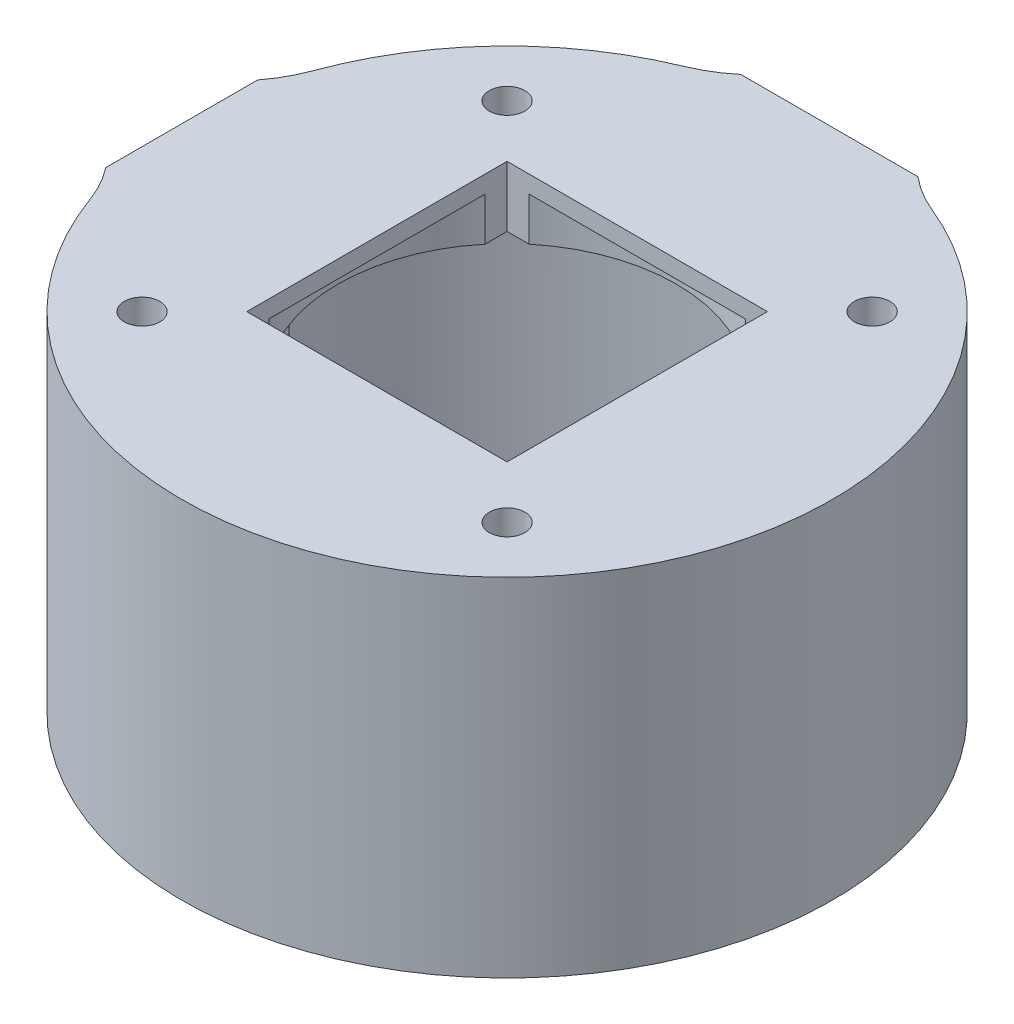
SolidWorks part; units mm, degrees
ref_plane "Спереди" through (0, 0, 0) normal (0, 0, 1) x (1, 0, 0)
ref_plane "Сверху" through (0, 0, 0) normal (0, 1, 0) x (1, 0, 0)
ref_plane "Справа" through (0, 0, 0) normal (1, 0, 0) x (0, 0, -1)
sketch "Sketch1" plane through (0, 0, 0) normal (0, 1, 0) x (1, 0, 0)
  circle A0 centre (0, 0) radius 70
  circle A1 centre (0, 0) radius 75
  dimension "D1" = 140
  dimension "D2" = 150
extrude "Boss-Extrude1" add sketch "Sketch1" along normal blind 60
sketch "Sketch2" plane through (0, 60, 0) normal (0, 1, 0) x (1, 0, 0)
  circle A0 centre (0, 0) radius 75
  circle A1 centre (0, 0) radius 75 construction
extrude "Boss-Extrude2" add sketch "Sketch2" along normal blind 20
sketch "Sketch3" plane through (0, 80, 0) normal (0, 1, 0) x (1, 0, 0)
  line L1 (42.0729, 42.0729) -> (-42.0729, 42.0729) construction
  line L2 (42.0729, 42.0729) -> (42.0729, -42.0729) construction
  line L3 (42.0729, -42.0729) -> (-42.0729, -42.0729) construction
  line L4 (-42.0729, 42.0729) -> (-42.0729, -42.0729) construction
  line L5 (42.0729, 42.0729) -> (-42.0729, -42.0729) construction
  line L6 (42.0729, -42.0729) -> (-42.0729, 42.0729) construction
  line L7 (22.5, 22.5) -> (-22.5, 22.5)
  line L8 (22.5, 22.5) -> (22.5, -22.5)
  line L9 (22.5, -22.5) -> (-22.5, -22.5)
  line L10 (-22.5, 22.5) -> (-22.5, -22.5)
  line L11 (22.5, 22.5) -> (-22.5, -22.5) construction
  line L12 (22.5, -22.5) -> (-22.5, 22.5) construction
  circle A0 centre (0, 0) radius 59.5 construction
  circle A1 centre (-42.0729, -42.0729) radius 4.1
  circle A2 centre (-42.0729, 42.0729) radius 4.1
  circle A3 centre (42.0729, 42.0729) radius 4.1
  circle A4 centre (42.0729, -42.0729) radius 4.1
  dimension "D1" = 119
  dimension "D2" = 8.2
  dimension "D3" = 45
extrude "Cut-Extrude1" cut sketch "Sketch3" against normal through all
sketch "Sketch5" plane through (0, 60, 0) normal (0, -1, 0) x (1, 0, 0)
  line L0 (0, 22.5) -> (0, 70) construction
  line L1 (-22.5, 22.5) -> (22.5, 22.5) construction
  line L3 (-22.5, 42.5) -> (22.5, 42.5)
  line L4 (-22.5, 42.5) -> (-22.5, 22.5)
  line L5 (-22.5, 22.5) -> (22.5, 22.5)
  line L6 (22.5, 42.5) -> (22.5, 22.5)
  line L7 (-22.5, 42.5) -> (22.5, 22.5) construction
  line L8 (-22.5, 22.5) -> (22.5, 42.5) construction
  circle A0 centre (0, 0) radius 70 construction
  point P7 (0, 32.5)
  dimension "D1" = 20
extrude "Cut-Extrude2" cut sketch "Sketch5" against normal blind 18
sketch "Sketch6" plane through (0, 60, 0) normal (0, -1, 0) x (1, 0, 0)
  circle A0 centre (0, 0) radius 51
  dimension "D1" = 102
extrude "Cut-Extrude3" cut sketch "Sketch6" against normal blind 6
sketch "Sketch7" plane through (0, 66, 0) normal (0, -1, 0) x (1, 0, 0)
  circle A0 centre (-42.0729, -42.0729) radius 7
  circle A1 centre (-42.0729, 42.0729) radius 7
  circle A2 centre (-42.0729, 42.0729) radius 4.1
  circle A3 centre (-42.0729, -42.0729) radius 4.1
  circle A4 centre (42.0729, -42.0729) radius 4.1
  circle A5 centre (42.0729, 42.0729) radius 4.1
  circle A6 centre (42.0729, -42.0729) radius 7
  circle A7 centre (42.0729, 42.0729) radius 7
  dimension "D1" = 14
extrude "Boss-Extrude3" add sketch "Sketch7" along normal up to surface (6 mm away) up to face at (0, 60, -51)
sketch "Sketch8" plane through (0, 66, 0) normal (0, -1, 0) x (1, 0, 0)
  circle A0 centre (0, 0) radius 39
  dimension "D1" = 78
extrude "Cut-Extrude4" cut sketch "Sketch8" against normal blind 10
sketch "Sketch9" plane through (0, 0, 0) normal (0, -1, 0) x (1, 0, 0)
  line L0 (0, -75) -> (0, 75) construction
  line L1 (7.5, -74.6241) -> (-7.5, -74.6241)
  circle A0 centre (0, 0) radius 75 construction
  point P8 (0, -74.6241)
  dimension "D1" = 15
extrude "Cut-Extrude5" cut sketch "Sketch9" against normal through all and the other way through all
sketch "Sketch10" plane through (0, 0, -74.6241) normal (0, 0, -1) x (-1, 0, 0)
  line L0 (0, 0) -> (0, 80) construction
  line L1 (-7.5, 0) -> (7.5, 0) construction
  line L2 (-7.5, 80) -> (7.5, 80) construction
  line L4 (-7.5, 20.4) -> (7.5, 20.4)
  line L5 (-7.5, 20.4) -> (-7.5, 7.6)
  line L6 (-7.5, 7.6) -> (7.5, 7.6)
  line L7 (7.5, 20.4) -> (7.5, 7.6)
  line L8 (-7.5, 20.4) -> (7.5, 7.6) construction
  line L9 (-7.5, 7.6) -> (7.5, 20.4) construction
  point P6 (0, 14)
  dimension "D1" = 12.8
  dimension "D2" = 15
  dimension "D3" = 14
  dimension "D4" = 20.4
extrude "Cut-Extrude6" cut sketch "Sketch10" against normal blind 10
sketch "Sketch11" plane through (0, 0, -74.6241) normal (0, 0, -1) x (-1, 0, 0)
  line L0 (0, 20.4) -> (0, 7.6) construction
  line L1 (7.5, 20.4) -> (-7.5, 20.4) construction
  line L2 (-7.5, 7.6) -> (7.5, 7.6) construction
  line L4 (-10, 4) -> (10, 4)
  line L5 (-10, 4) -> (-10, 24)
  line L6 (-10, 24) -> (10, 24)
  line L7 (10, 4) -> (10, 24)
  line L8 (-10, 4) -> (10, 24) construction
  line L9 (-10, 24) -> (10, 4) construction
  point P6 (0, 14)
  dimension "D1" = 20
  dimension "D2" = 20
extrude "Cut-Extrude7" cut sketch "Sketch11" against normal blind 10 from offset 3 offset against normal yes
sketch "Sketch12" plane through (0, 60, 0) normal (0, -1, 0) x (1, 0, 0)
  line L0 (0, -51) -> (0, 70) construction
  circle A0 centre (0, 0) radius 51 construction
  circle A1 centre (0, 0) radius 70 construction
  circle A2 centre (0, -51) radius 7.5
  dimension "D1" = 15
extrude "Cut-Extrude8" cut sketch "Sketch12" against normal up to surface (6 mm away) up to face at (0, 66, 19.4638)
sketch "Sketch13" plane through (0, 60, 0) normal (0, -1, 0) x (1, 0, 0)
  line L0 (-47.9479, -51) -> (0, -51) construction
  circle A0 centre (0, 0) radius 70 construction
  arc A1 (7.4797, -50.4485) -> (-7.4797, -50.4485) centre (0, 0) ccw construction
  circle A2 centre (0, -51) radius 10.5
  dimension "D1" = 21
extrude "Cut-Extrude9" cut sketch "Sketch13" against normal up to surface (6 mm away) and the other way through all up to face at (0, 66, -3.75)
sketch "Sketch14" plane through (0, 0, 0) normal (0, -1, 0) x (1, 0, 0)
  line L0 (0, 0) -> (0, -110.0571) construction
  line L2 (10, -94.282) -> (-10, -94.282)
  line L3 (10, -94.282) -> (10, -69.282)
  line L4 (10, -69.282) -> (-10, -69.282) construction
  line L5 (-10, -94.282) -> (-10, -69.282)
  line L6 (10, -94.282) -> (-10, -69.282) construction
  line L7 (10, -69.282) -> (-10, -94.282) construction
  arc A0 (-10, -69.282) -> (10, -69.282) centre (0, 0) ccw construction
  circle A1 centre (0, 0) radius 70 construction
  arc A2 (10, -69.282) -> (-10, -69.282) centre (0, 0) cw
  point P6 (0, -70)
  point P7 (0, -81.782)
  dimension "D1" = 20
  dimension "D2" = 25
  dimension "D3" = 81.782
extrude "Boss-Extrude4" add sketch "Sketch14" against normal up to surface (80 mm away) up to face at (-42.0729, 80, -37.9729)
sketch "Sketch15" plane through (0, 0, 0) normal (0, -1, 0) x (1, 0, 0)
  line L0 (0, -59.1608) -> (0, -94.282) construction
  line L2 (-10, -94.282) -> (10, -94.282) construction
  line L4 (7.55, -91.5916) -> (-7.55, -91.5916)
  line L5 (7.55, -91.5916) -> (7.55, -69.5916)
  line L6 (7.55, -69.5916) -> (-7.55, -69.5916)
  line L7 (-7.55, -91.5916) -> (-7.55, -69.5916)
  line L8 (7.55, -91.5916) -> (-7.55, -69.5916) construction
  line L9 (7.55, -69.5916) -> (-7.55, -91.5916) construction
  circle A0 centre (0, 0) radius 70 construction
  point P6 (0, -80.5916)
  dimension "D1" = 15.1
  dimension "D2" = 22
extrude "Cut-Extrude10" cut sketch "Sketch15" against normal blind 20.4
fillet "Fillet1" radius 30 2 edges at (10, 40, -74.3303) (-10, 40, -74.3303)
sketch "Sketch16" plane through (0, 20.4, 0) normal (0, -1, 0) x (1, 0, 0)
  line L0 (0, -70) -> (0, -91.5916) construction
  line L1 (-7.55, -91.5916) -> (7.55, -91.5916) construction
  line L3 (7.55, -76.1916) -> (-7.55, -76.1916)
  line L4 (7.55, -76.1916) -> (7.55, -91.5916)
  line L5 (7.55, -91.5916) -> (-7.55, -91.5916)
  line L6 (-7.55, -76.1916) -> (-7.55, -91.5916)
  line L7 (7.55, -76.1916) -> (-7.55, -91.5916) construction
  line L8 (7.55, -91.5916) -> (-7.55, -76.1916) construction
  arc A0 (-7.55, -69.5916) -> (7.55, -69.5916) centre (0, 0) ccw construction
  point P7 (0, -83.8916)
  dimension "D1" = 15.4
extrude "Cut-Extrude11" cut sketch "Sketch16" against normal blind 2
sketch "Sketch17" plane through (0, 0, -91.5916) normal (0, 0, 1) x (1, 0, 0)
  line L0 (0, 22.4) -> (0, 0) construction
  line L1 (-7.55, 22.4) -> (7.55, 22.4) construction
  line L2 (-7.55, 0) -> (7.55, 0) construction
  line L4 (7.55, 9.6) -> (-7.55, 9.6)
  line L5 (7.55, 9.6) -> (7.55, 22.4)
  line L6 (7.55, 22.4) -> (-7.55, 22.4)
  line L7 (-7.55, 9.6) -> (-7.55, 22.4)
  line L8 (7.55, 9.6) -> (-7.55, 22.4) construction
  line L9 (7.55, 22.4) -> (-7.55, 9.6) construction
  point P6 (0, 16)
  dimension "D1" = 12.8
  dimension "D2" = 15.1
extrude "Cut-Extrude12" cut sketch "Sketch17" against normal through all
chamfer "Chamfer1" distance 20 angle 65 1 edges at (0, 80, -94.282) first distance on face at (0, 80, -44.4515)
sketch "Sketch19" plane through (0, 20.4, 0) normal (0, -1, 0) x (1, 0, 0)
  line L0 (7.55, -72.2416) -> (-7.55, -72.2416) construction
  line L1 (7.55, -76.1916) -> (7.55, -69.5916) construction
  line L2 (-7.55, -69.5916) -> (-7.55, -76.1916) construction
  line L4 (-7.55, -74.8916) -> (7.55, -74.8916)
  line L5 (-7.55, -74.8916) -> (-7.55, -69.5916)
  line L6 (-7.55, -69.5916) -> (7.55, -69.5916) construction
  line L7 (7.55, -74.8916) -> (7.55, -69.5916)
  line L8 (-7.55, -74.8916) -> (7.55, -69.5916) construction
  line L9 (-7.55, -69.5916) -> (7.55, -74.8916) construction
  arc A4 (-7.55, -69.5916) -> (7.55, -69.5916) centre (0, 0) ccw
  arc A5 (7.55, -69.5916) -> (-7.55, -69.5916) centre (0, 0) ccw construction
  point P6 (0, -72.2416)
  dimension "D1" = 5.3
extrude "Boss-Extrude5" add sketch "Sketch19" along normal blind 5
sketch "Sketch20" plane through (0, 0, 0) normal (0, -1, 0) x (1, 0, 0)
  line L0 (0, 0) -> (-75, 0) construction
  line L2 (-65, -15) -> (-75, -15)
  line L3 (-65, -15) -> (-65, 15)
  line L4 (-65, 15) -> (-75, 15)
  line L5 (-75, -15) -> (-75, 15)
  line L6 (-65, -15) -> (-75, 15) construction
  line L7 (-65, 15) -> (-75, -15) construction
  arc A0 (28.4741, -69.3846) -> (-28.4741, -69.3846) centre (0, 0) ccw construction
  point P7 (-70, 0)
  point P12 (0, 0)
  point P13 (0, 0)
  point P14 (0, 0)
  point P15 (0, 0)
  point P16 (0, 0)
  point P17 (-75, 0)
  dimension "D1" = 10
  dimension "D2" = 30
extrude "Cut-Extrude13" cut sketch "Sketch20" against normal blind 30 from offset 20 offset against normal yes
sketch "Sketch21" plane through (0, 50, 0) normal (0, -1, 0) x (1, 0, 0)
  line L0 (-67.7772, 17.5) -> (-67.7772, -17.5)
  line L3 (-65.8886, 0) -> (-71.3886, 0) construction
  line L4 (-75, -17.5) -> (-67.7772, -17.5)
  line L5 (-75, -17.5) -> (-75, 17.5)
  line L6 (-75, 17.5) -> (-67.7772, 17.5)
  line L8 (-75, -17.5) -> (-67.7772, 17.5) construction
  line L9 (-75, 17.5) -> (-67.7772, -17.5) construction
  arc A1 (-73.4847, 15) -> (-73.4847, -15) centre (0, 0) ccw construction
  circle A3 centre (0, 0) radius 70 construction
  point P0 (0, 0)
  point P3 (-75, 0)
  point P12 (-71.3886, 0)
  dimension "D1" = 35
extrude "Boss-Extrude6" add sketch "Sketch21" along normal up to surface (50 mm away) and the other way up to surface (30 mm away) up to face at (0, 0, -45.6937) other way up to face at (0, 80, -35.5784)
sketch "Sketch22" plane through (-67.7772, 0, 0) normal (1, 0, 0) x (0, 0, -1)
  line L0 (0, 0) -> (0, 60) construction
  line L1 (-17.5, 0) -> (17.5, 0) construction
  line L2 (15, 60) -> (-15, 60)
  line L3 (-15, 60) -> (-15, 30)
  line L4 (17.5, 60) -> (-17.5, 60) construction
  line L5 (-15, 30) -> (15, 30)
  line L6 (15, 30) -> (15, 60)
  line L7 (17.5, 60) -> (-17.5, 60) construction
  point P8 (0, 0)
  point P9 (0, 52.3023)
  point P12 (0, 60)
  dimension "D2" = 30
  dimension "D3" = 30
extrude "Cut-Extrude15" cut sketch "Sketch22" against normal through all
fillet "Fillet2" radius 30 2 edges at (-72.9298, 40, -17.5) (-72.9298, 40, 17.5)
sketch "Sketch23" plane through (0, 80, 0) normal (0, 1, 0) x (1, 0, 0)
  line L1 (-30, 30) -> (30, 30)
  line L2 (-30, 30) -> (-30, -30)
  line L3 (-30, -30) -> (30, -30)
  line L4 (30, 30) -> (30, -30)
  line L5 (-30, 30) -> (30, -30) construction
  line L6 (-30, -30) -> (30, 30) construction
  point P0 (0, 0)
  dimension "D1" = 60
  dimension "D2" = 60
extrude "Cut-Extrude16" cut sketch "Sketch23" against normal through all
